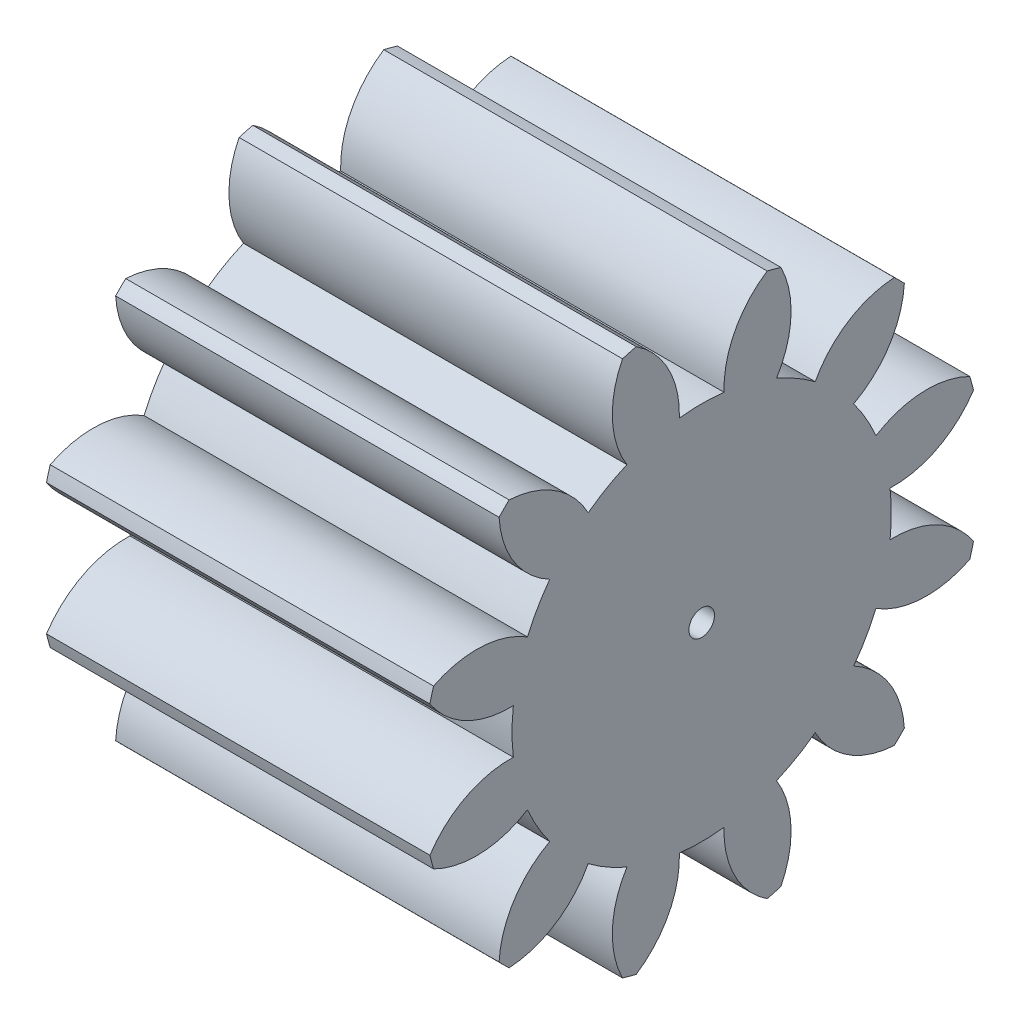
SolidWorks part; units mm, degrees
ref_plane "Plane1" through (0, 0, 0) normal (0, 0, 1) x (1, 0, 0)
ref_plane "Plane2" through (0, 0, 0) normal (0, 1, 0) x (1, 0, 0)
ref_plane "Plane3" through (0, 0, 0) normal (1, 0, 0) x (0, 0, -1)
sketch "HoldingSke" plane through (0, 0, 0) normal (0, 1, 0) x (1, 0, 0)
  line L0 (0, 0) -> (0.7825, -0.1663)
  line L1 (-15, 0) -> (100, 0) construction
  line L2 (0, 0) -> (-2.1039, 2.3779)
  line L3 (0, 0) -> (-11.863, 4.5341)
  line L4 (0, 0) -> (8.4473, 1.7955)
  line L5 (0, 0) -> (-46.8476, -17.4728)
  line L6 (0, 0) -> (-9.9476, -6.7116)
  line L7 (-2.1039, 2.3779) -> (8.6586, 51.2059)
  line L8 (-76.2, 54.61) -> (-76.1, 54.61)
  line L9 (-71.009, 38.7566) -> (-53.1078, 45.2721)
  line L10 (-76.2, 71.12) -> (104.1128, 71.12)
  line L11 (0, 0) -> (-12, 0)
  line L12 (-76.2, 101.6) -> (-76.155, 101.6)
  line L13 (24.9733, 27.94) -> (52.9518, 28.4284)
  line L14 (24.9733, 27.94) -> (24.9743, 27.94)
  line L15 (24.9733, 27.94) -> (100.4006, 29.5858)
  line L16 (-63.627, -1.25) -> (-12.827, -1.25)
  circle A0 centre (0, 0) radius 0.4
  circle A1 centre (0, 0) radius 5.9365
  circle A2 centre (0, 0) radius 37.5
  circle A3 centre (0, 0) radius 0.4
  dimension "MHD" = 11.873
  dimension "Hub_dia" = 75
  dimension "Bore" = 0.8
  dimension "MBD" = 0.8
  dimension "Num_teeth" = 12
  dimension "Pitch_radius" = 180.3128
  dimension "Pitch" = 0.8
  dimension "Width" = 12
  dimension "Overall_len" = 50
  dimension "Show_teeth" = 12
  dimension "Thickness" = 12
  dimension "OAL" = 50.0001
  dimension "T_dim" = 0.1
  dimension "Ap" = 20
  dimension "H" = 19.05
  dimension "Backlash" = 0.045
  dimension "Addendum_fac" = 1
  dimension "Dedendum_fac" = 1.25
  dimension "Clearance_fac" = 0.25
  dimension "Dedendum_add" = 0.001
  dimension "Module" = 1.25
sketch "BasProSke" plane through (0, 0, 0) normal (0, 1, 0) x (1, 0, 0)
  line L0 (-10, 0) -> (60, 0) construction
  line L1 (0, 0) -> (0, 8.75)
  line L2 (0, 0) -> (12, 0)
  line L3 (12, 0) -> (12, 8.75)
  line L4 (12, 8.75) -> (0, 8.75)
  dimension "Diameter" = 17.5
  dimension "Thickness" = 12
revolve "Base-Revolve" add sketch "BasProSke" angle 360 about L0
sketch "TooCutSke" plane through (0, 0, 0) normal (1, 0, 0) x (0, 0, -1)
  line L1 (0, 0) -> (0, 107) construction
  line L2 (0, 0) -> (-1.0576, 7.4251) construction
  line L3 (0, 0) -> (-3.8542, 14.3841) construction
  line L4 (-1.0576, 7.4251) -> (-1.9271, 7.1921) construction
  arc A0 (0.6993, 5.8952) -> (-0.6993, 5.8952) centre (0, 0) ccw
  arc A1 (2.0786, 8.5257) -> (-2.0786, 8.5257) centre (0, 0) ccw
  circle A2 centre (0, 0) radius 7.5 construction
  circle A3 centre (0, 0) radius 7.0477 construction
  arc A4 (-0.6993, 5.8952) -> (-2.0786, 8.5257) centre (-3.6975, 5.9999) ccw
  arc A5 (2.0786, 8.5257) -> (0.6993, 5.8952) centre (3.6975, 5.9999) ccw
  dimension "Root_dia" = 11.873
  dimension "Overcut_dia" = 17.5508
  dimension "Pitch_dia" = 15
  dimension "Base_dia" = 14.0954
  dimension "Flank_rad" = 3
  dimension "Half_ang" = 15
  dimension "Half_CT" = 0.9002
extrude "ToothCut" cut sketch "TooCutSke" along normal through all
fillet "Breaks" [suppressed] radius 0.025 tangent propagation no
fillet "RootFillets" [suppressed] radius 0.3135
pattern_circular "TeethCuts" count 12 every 30 about axis through (-10, 0, 0) along (1, 0, 0) of "ToothCut", "RootFillets", "Breaks"
sketch "HubNeaOneSke" plane through (0, 0, 0) normal (-1, 0, 0) x (0, 0, 1)
  circle A0 centre (0, 0) radius 5.9365
  dimension "Diameter" = 11.873
extrude "HubNearOne" [suppressed] add sketch "HubNeaOneSke" along normal blind 38.0001
sketch "HubNeaBotSke" plane through (0, 0, 0) normal (-1, 0, 0) x (0, 0, 1)
  circle A0 centre (0, 0) radius 5.9365
  dimension "Diameter" = 11.873
extrude "HubNearBoth" [suppressed] add sketch "HubNeaBotSke" along normal blind 19
ref_plane "FarPln" through (12, 0, 0) normal (1, 0, 0) x (0, 0, -1)
sketch "HubFarSke" plane through (12, 0, 0) normal (1, 0, 0) x (0, 0, -1)
  circle A0 centre (0, 0) radius 5.9365
  dimension "Diameter" = 11.873
extrude "HubFar" [suppressed] add sketch "HubFarSke" along normal blind 19
sketch "BorSke" plane through (0, 0, 0) normal (1, 0, 0) x (0, 0, -1)
  circle A0 centre (0, 0) radius 0.4
  dimension "Diameter" = 0.8
extrude "Bore" cut sketch "BorSke" along normal mid plane 100.0001
sketch "KeySke" plane through (0, 0, 0) normal (1, 0, 0) x (0, 0, -1)
  line L0 (-0.05, 0) -> (-0.05, 0.5)
  line L1 (-0.05, 0.5) -> (0.05, 0.5)
  line L2 (0.05, 0.5) -> (0.05, 0)
  line L3 (0, 0) -> (0, 34) construction
  line L4 (-0.05, 0) -> (0.05, 0)
  dimension "Offset" = 0.5
  dimension "Width" = 0.1
extrude "Keyway" [suppressed] cut sketch "KeySke" along normal mid plane 100.0001
pattern_circular "Keyway2" [suppressed] count 2 every 90 about axis through (-10, 0, 0) along (1, 0, 0)
equation "' \"Module@HoldingSke\" = 6.35"
equation "' \"Num_teeth@HoldingSke\" = 12"
equation "' \"Ap@HoldingSke\" =  20"
equation "' \"Width@HoldingSke\" = 0.5 * 25.4"
equation "' \"Hub_dia@HoldingSke\"= 1 * 25.4"
equation "' \"Overall_len@HoldingSke\" = 1.0 * 25.4"
equation "' \"Bore@HoldingSke\" = 0.75 * 25.4"
equation "' \"T_dim@HoldingSke\" = 0.1 * 25.4"
equation "' \"Width@KeySke\" = 0.25 * 25.4"
equation "' \"Show_teeth@HoldingSke\" = 13"
equation "' \"Backlash@HoldingSke\" = 0.009 * 25.4"
equation "' \"Addendum_fac@HoldingSke\" = 1.0"
equation "' \"Dedendum_fac@HoldingSke\" = 1.25"
equation "' \"Dedendum_add@HoldingSke\" = 0.00005 * 25.4"
equation "' \"Clearance_fac@HoldingSke\" = 0.25"
equation "\"Pitch@HoldingSke\" = 1 / \"Module@HoldingSke\""
equation "\"Overcut_dia@TooCutSke\" = (\"Num_teeth@HoldingSke\" + 2 * \"Addendum_fac@HoldingSke\") / \"Pitch@HoldingSke\" + 0.002 * 25.4"
equation "\"Pitch_dia@TooCutSke\" = \"Num_teeth@HoldingSke\" / \"Pitch@HoldingSke\""
equation "\"Base_dia@TooCutSke\" = \"Num_teeth@HoldingSke\" / \"Pitch@HoldingSke\" * cos((\"Ap@HoldingSke\"  * 3.14159265 / 180))"
equation "\"Root_dia@TooCutSke\" = (\"Num_teeth@HoldingSke\" + 2) / \"Pitch@HoldingSke\" - 2 * (\"Addendum_fac@HoldingSke\" + \"Dedendum_fac@HoldingSke\") / \"Pitch@HoldingSke\" - \"Dedendum_add@HoldingSke\" * 2"
equation "\"Half_ang@TooCutSke\" = 180 / \"Num_teeth@HoldingSke\""
equation "\"Half_CT@TooCutSke\" = \"Num_teeth@HoldingSke\" / \"Pitch@HoldingSke\" * sin((3.14159265 / 2 / \"Num_teeth@HoldingSke\")) / 2 - 7 * \"Backlash@HoldingSke\" / 4"
equation "\"Flank_rad@TooCutSke\" = \"Num_teeth@HoldingSke\" / \"Pitch@HoldingSke\" / 5"
equation "\"Radius@RootFillets\" = \"Clearance_fac@HoldingSke\" / \"Pitch@HoldingSke\" + \"Dedendum_add@HoldingSke\""
equation "\"Break_rad@Breaks\" = 0.02 / \"Pitch@HoldingSke\""
equation "\"Thickness@HoldingSke\" = \"Width@HoldingSke\""
equation "\"OAL@HoldingSke\" = \"Thickness@HoldingSke\""
equation "\"MHD@HoldingSke\" = (\"Num_teeth@HoldingSke\" + 2) / \"Pitch@HoldingSke\" - 2 * (\"Addendum_fac@HoldingSke\" + \"Dedendum_fac@HoldingSke\")  / \"Pitch@HoldingSke\" - \"Dedendum_add@HoldingSke\" * 2"
equation "\"MBD@HoldingSke\" = (\"Num_teeth@HoldingSke\" + 2) / \"Pitch@HoldingSke\" - 2 * (\"Addendum_fac@HoldingSke\" + \"Dedendum_fac@HoldingSke\")  / \"Pitch@HoldingSke\" - \"Dedendum_add@HoldingSke\" * 2 - 0.002 * 25.4"
equation "\"MHD@HoldingSke\" = ((sgn( \"MHD@HoldingSke\" - \"Hub_dia@HoldingSke\" )-1)*( \"MHD@HoldingSke\" - \"Hub_dia@HoldingSke\" ))/-2+ \"Hub_dia@HoldingSke\""
equation "\"MBD@HoldingSke\" = ((sgn( \"MBD@HoldingSke\" - \"Bore@HoldingSke\" )-1)*( \"MBD@HoldingSke\" - \"Bore@HoldingSke\" ))/-2+ \"Bore@HoldingSke\""
equation "\"OAL@HoldingSke\" = ((sgn( \"OAL@HoldingSke\" - \"Overall_len@HoldingSke\" )+1)*( \"OAL@HoldingSke\" - \"Overall_len@HoldingSke\" ))/2 + \"Overall_len@HoldingSke\" + 0.000002 * 25.4"
equation "\"Num_teeth@TeethCuts\" = int( \"Show_teeth@HoldingSke\" ) + 1"
equation "\"Num_teeth@TeethCuts\" = ((sgn( \"Num_teeth@TeethCuts\" - \"Num_teeth@HoldingSke\" )-1)*( \"Num_teeth@TeethCuts\" - \"Num_teeth@HoldingSke\" ))/-2+ \"Num_teeth@HoldingSke\""
equation "\"Num_teeth@TeethCuts\" = ((sgn( \"Num_teeth@TeethCuts\" - 2.0)+1)*( \"Num_teeth@TeethCuts\" - 2.0))/2 +2.0"
equation "\"Angle@TeethCuts\" = 360.0 / \"Num_teeth@HoldingSke\""
equation "\"Diameter@BasProSke\" = (\"Num_teeth@HoldingSke\" + 2 * \"Addendum_fac@HoldingSke\") / \"Pitch@HoldingSke\""
equation "\"Thickness@BasProSke\"  = \"Thickness@HoldingSke\""
equation "' \"Fillet_rad@BasProSke\" =  \"Thickness@HoldingSke\" * 0.05"
equation "\"MHD@HoldingSke\" = ((sgn( \"MHD@HoldingSke\" - \"Root_dia@TooCutSke\" )-1)*( \"MHD@HoldingSke\" - \"Root_dia@TooCutSke\" ))/-2+ \"Root_dia@TooCutSke\""
equation "\"Diameter@HubNeaOneSke\" = \"MHD@HoldingSke\""
equation "\"Length@HubNearOne\" = \"OAL@HoldingSke\" - \"Thickness@BasProSke\""
equation "\"Diameter@HubNeaBotSke\" = \"MHD@HoldingSke\""
equation "\"Length@HubNearBoth\" = ( \"OAL@HoldingSke\" - \"Thickness@BasProSke\" ) / 2.0"
equation "\"Thickness@FarPln\" = \"Thickness@BasProSke\""
equation "\"Diameter@HubFarSke\" = \"MHD@HoldingSke\""
equation "\"Length@HubFar\" = ( \"OAL@HoldingSke\" - \"Thickness@BasProSke\" ) / 2.0"
equation "\"Diameter@BorSke\" = \"MBD@HoldingSke\""
equation "\"D1@Bore\" = \"OAL@HoldingSke\" * 2.0"
equation "\"D1@Keyway\" = \"OAL@HoldingSke\" * 2.0"
equation "\"Offset@KeySke\" = \"T_dim@HoldingSke\" + \"MBD@HoldingSke\" / 2.0"
